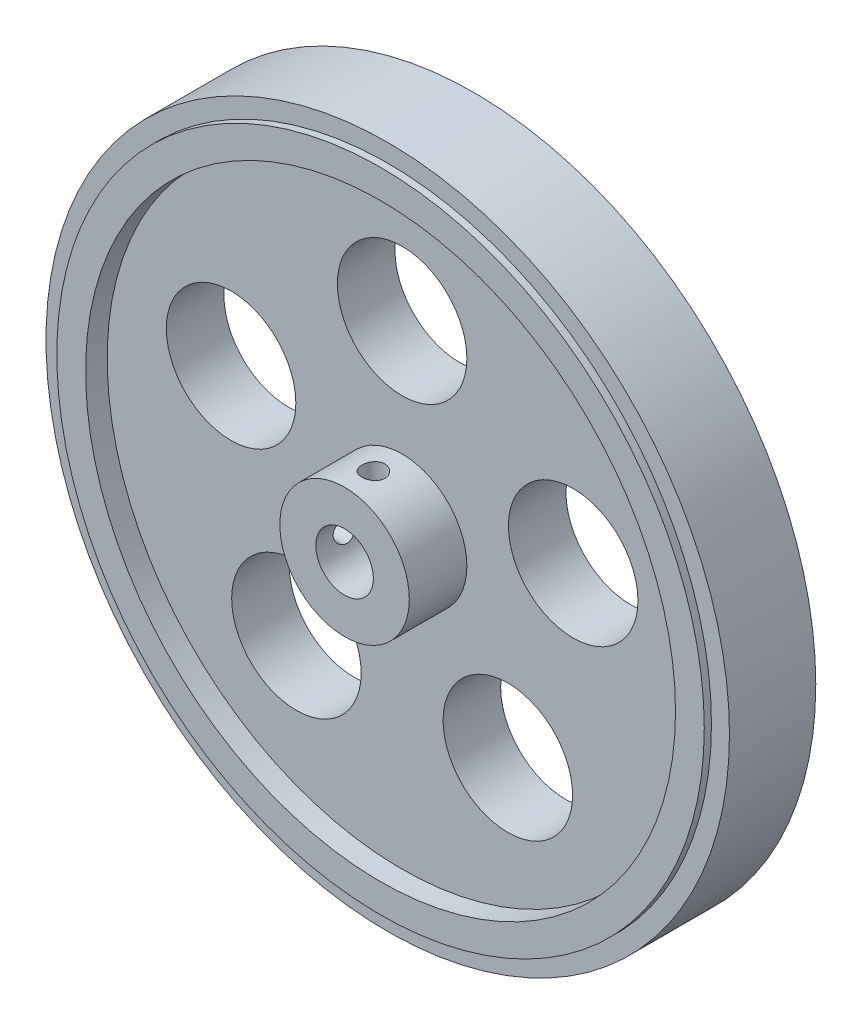
SolidWorks part; units mm, degrees
ref_plane "Front Plane" through (0, 0, 0) normal (0, 0, 1) x (1, 0, 0)
ref_plane "Top Plane" through (0, 0, 0) normal (0, 1, 0) x (1, 0, 0)
ref_plane "Right Plane" through (0, 0, 0) normal (1, 0, 0) x (0, 0, -1)
sketch "Sketch1" plane through (0, 0, 0) normal (0, 0, 1) x (1, 0, 0)
  circle A0 centre (0, 0) radius 47.5
  dimension "D1" = 95
extrude "Boss-Extrude1" add sketch "Sketch1" along normal blind 6 and the other way blind 6
sketch "Sketch2" plane through (0, 0, 6) normal (0, 0, 1) x (1, 0, 0)
  circle A0 centre (0, 0) radius 45
  dimension "D1" = 90
extrude "Boss-Extrude2" add sketch "Sketch2" along normal blind 1
sketch "Sketch3" plane through (0, 0, -6) normal (0, 0, -1) x (-1, 0, 0)
  circle A0 centre (0, 0) radius 45
  dimension "D1" = 90
extrude "Boss-Extrude3" add sketch "Sketch3" along normal blind 1
sketch "Sketch4" plane through (0, 0, -7) normal (0, 0, -1) x (-1, 0, 0)
  circle A0 centre (0, 0) radius 9
  dimension "D1" = 18
extrude "Boss-Extrude4" add sketch "Sketch4" along normal blind 0.2
sketch "Sketch5" plane through (0, 0, 7) normal (0, 0, 1) x (1, 0, 0)
  circle A0 centre (0, 0) radius 9
  dimension "D1" = 18
extrude "Boss-Extrude5" add sketch "Sketch5" along normal blind 5
sketch "Sketch6" plane through (0, 0, 7) normal (0, 0, 1) x (1, 0, 0)
  circle A0 centre (0, 0) radius 41
  circle A1 centre (0, 0) radius 9
  dimension "D1" = 82
  dimension "D2" = 18
extrude "Cut-Extrude1" cut sketch "Sketch6" against normal blind 3
sketch "Sketch7" plane through (0, 0, -7) normal (0, 0, -1) x (-1, 0, 0)
  circle A0 centre (0, 0) radius 9
  circle A1 centre (0, 0) radius 41
  dimension "D1" = 18
  dimension "D2" = 82
extrude "Cut-Extrude2" cut sketch "Sketch7" against normal blind 3
sketch "Sketch8" plane through (0, 0, -4) normal (0, 0, -1) x (-1, 0, 0)
  circle A0 centre (0, 25) radius 9
  circle A1 centre (23.7764, 7.7254) radius 9
  circle A2 centre (14.6946, -20.2254) radius 9
  circle A3 centre (-14.6946, -20.2254) radius 9
  circle A4 centre (-23.7764, 7.7254) radius 9
  point P2 (25.7957, 8.3815)
  point P3 (31.6609, 8.5598)
  point P5 (0, 0)
  point P14 (0, 0)
  dimension "D1" = 18
  dimension "D2" = 5
  dimension "D3" = 25
extrude "Cut-Extrude3" cut sketch "Sketch8" against normal through all
sketch "Sketch9" plane through (0, 0, 12) normal (0, 0, 1) x (1, 0, 0)
  circle A0 centre (0, 0) radius 4
  dimension "D1" = 8
extrude "Cut-Extrude4" cut sketch "Sketch9" against normal through all
ref_plane "Plane1" through (-9, 0, 0) normal (-1, 0, 0) x (0, 0, 1)
sketch "Sketch10" plane through (-9, 0, 0) normal (-1, 0, 0) x (0, 0, 1)
  line L0 (12, -9) -> (12, 9) construction
  circle A0 centre (8, 0) radius 1.6
  point P2 (0, 0)
  dimension "D1" = 3.2
  dimension "D2" = 4
extrude "Cut-Extrude5" cut sketch "Sketch10" against normal up to next
ref_plane "Plane2" through (0, 9, 0) normal (0, 1, 0) x (1, 0, 0)
sketch "Sketch11" plane through (0, 9, 0) normal (0, 1, 0) x (1, 0, 0)
  line L0 (-9, -12) -> (9, -12) construction
  circle A0 centre (0, -8) radius 1.6
  point P2 (0, 0)
  dimension "D1" = 3.2
  dimension "D2" = 4
extrude "Cut-Extrude6" cut sketch "Sketch11" against normal up to next
